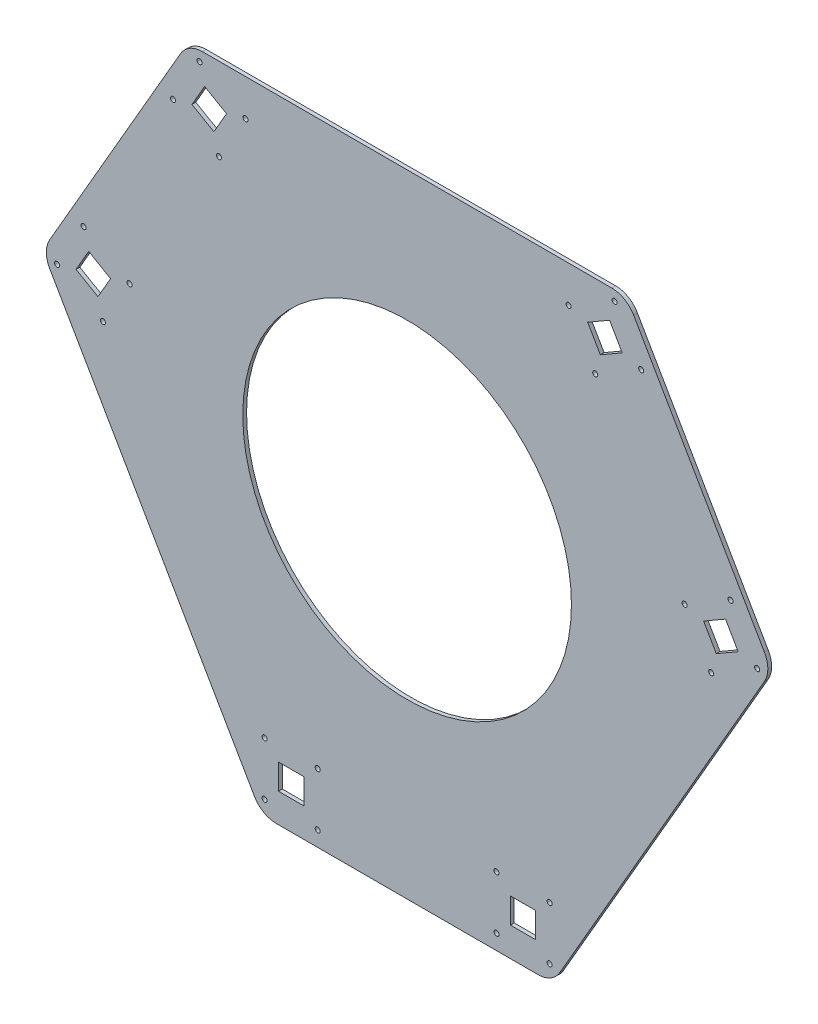
SolidWorks part; units mm, degrees
ref_plane "前视基准面" through (0, 0, 0) normal (0, 0, 1) x (1, 0, 0)
ref_plane "上视基准面" through (0, 0, 0) normal (0, 1, 0) x (1, 0, 0)
ref_plane "右视基准面" through (0, 0, 0) normal (1, 0, 0) x (0, 0, -1)
other "Configuration Table"
sketch "草图1" plane through (0, 0, 0) normal (0, 0, 1) x (1, 0, 0)
  line L0 (173.4394, 232.9258) -> (-173.4394, 232.9258)
  line L1 (-173.4394, 232.9258) -> (-288.4394, 33.74)
  line L2 (-288.4394, 33.74) -> (-115, -266.6658)
  line L3 (-115, -266.6658) -> (115, -266.6658)
  line L4 (115, -266.6658) -> (288.4394, 33.74)
  line L5 (288.4394, 33.74) -> (173.4394, 232.9258)
  line L6 (-230.9394, 133.3329) -> (201.7197, -116.4629) construction
  line L7 (0, 232.9258) -> (0, -266.6658) construction
  circle A0 centre (0, 0) radius 130
  circle A1 centre (164.1865, 224.9521) radius 2
  circle A2 centre (185.1865, 188.579) radius 2
  circle A3 centre (148.8135, 167.579) radius 2
  circle A4 centre (127.8135, 203.9521) radius 2
  circle A5 centre (185.1865, 188.579) radius 2
  circle A6 centre (148.8135, 167.579) radius 2
  circle A7 centre (164.1865, 224.9521) radius 2
  circle A8 centre (127.8135, 203.9521) radius 2
  circle A9 centre (255.9075, 66.0867) radius 2
  circle A10 centre (276.9075, 29.7137) radius 2
  circle A11 centre (240.5344, 8.7137) radius 2
  circle A12 centre (219.5344, 45.0867) radius 2
  circle A13 centre (-164.1865, 224.9521) radius 2
  circle A14 centre (-127.8135, 203.9521) radius 2
  circle A15 centre (-185.1865, 188.579) radius 2
  circle A16 centre (-148.8135, 167.579) radius 2
  circle A17 centre (185.1865, 188.579) radius 2
  circle A18 centre (185.1865, 188.579) radius 2
  circle A19 centre (148.8135, 167.579) radius 2
  circle A20 centre (148.8135, 167.579) radius 2
  circle A21 centre (185.1865, 188.579) radius 2
  circle A22 centre (148.8135, 167.579) radius 2
  circle A23 centre (-219.5344, 45.0867) radius 2 construction
  circle A24 centre (-219.5344, 45.0867) radius 2
  circle A25 centre (-255.9075, 66.0867) radius 2 construction
  circle A26 centre (-255.9075, 66.0867) radius 2
  circle A27 centre (-276.9075, 29.7137) radius 2 construction
  circle A28 centre (-276.9075, 29.7137) radius 2
  circle A29 centre (-240.5344, 8.7137) radius 2 construction
  circle A30 centre (-240.5344, 8.7137) radius 2
  circle A31 centre (-112.7209, -212.6657) radius 2 construction
  circle A32 centre (-112.7209, -212.6657) radius 2
  circle A33 centre (-70.7209, -212.6657) radius 2 construction
  circle A34 centre (-70.7209, -212.6657) radius 2
  circle A35 centre (-112.7209, -254.6657) radius 2 construction
  circle A36 centre (-112.7209, -254.6657) radius 2
  circle A37 centre (-70.7209, -254.6657) radius 2 construction
  circle A38 centre (-70.7209, -254.6657) radius 2
  circle A39 centre (112.7209, -254.6657) radius 2 construction
  circle A40 centre (112.7209, -254.6657) radius 2
  circle A41 centre (70.7209, -254.6657) radius 2 construction
  circle A42 centre (70.7209, -254.6657) radius 2
  circle A43 centre (70.7209, -212.6657) radius 2 construction
  circle A44 centre (70.7209, -212.6657) radius 2
  circle A45 centre (112.7209, -212.6657) radius 2 construction
  circle A46 centre (112.7209, -212.6657) radius 2
  point P7 (0, 0)
  point P70 (-122.2962, -44.0868)
  dimension "D7" = 120
  dimension "D3" = 260
  dimension "D1" = 120
  dimension "D2" = 120
  dimension "D4" = 120
  dimension "D5" = 120
  dimension "D6" = 230
extrude "凸台-拉伸1" add sketch "草图1" along normal blind 3 contours L4 L5 L0 L1 L2 L3 A0 | L5 L0 L1 L2 L3 L4 | A0 | A28 | A46 | A40 | A42 | A44 | A34 | A32 | A38 | A36 | A26 | A24 | A30 | A14 | A16 | A15 | A13 | A10 | A11 | A12 | A9 | A3 | A5 | A7 | A4 region at (224.3304, 129.5172, 0)
sketch "草图8" plane through (0, 0, 3) normal (0, 0, 1) x (1, 0, 0)
  line L0 (-160.1603, 209.9258) -> (-170.1603, 192.6053)
  line L1 (-160.1603, 209.9258) -> (-142.8398, 199.9258)
  line L2 (-170.1603, 192.6053) -> (-152.8398, 182.6053)
  line L3 (-142.8398, 199.9258) -> (-152.8398, 182.6053)
  line L4 (-173.4394, 232.9258) -> (-288.4394, 33.74) construction
  line L5 (-251.8813, 51.0605) -> (-261.8813, 33.74)
  line L6 (-251.8813, 51.0605) -> (-234.5608, 41.0605)
  line L7 (-261.8813, 33.74) -> (-244.5608, 23.74)
  line L8 (-234.5608, 41.0605) -> (-244.5608, 23.74)
  line L9 (-101.7209, -243.6658) -> (-81.7209, -243.6658)
  line L10 (-101.7209, -243.6658) -> (-101.7209, -223.6658)
  line L11 (-81.7209, -243.6658) -> (-81.7209, -223.6658)
  line L12 (-101.7209, -223.6658) -> (-81.7209, -223.6658)
  line L13 (81.7209, -243.6658) -> (101.7209, -243.6658)
  line L14 (81.7209, -243.6658) -> (81.7209, -223.6658)
  line L15 (101.7209, -243.6658) -> (101.7209, -223.6658)
  line L16 (81.7209, -223.6658) -> (101.7209, -223.6658)
  line L17 (261.8813, 33.74) -> (251.8813, 51.0605)
  line L18 (261.8813, 33.74) -> (244.5608, 23.74)
  line L19 (251.8813, 51.0605) -> (234.5608, 41.0605)
  line L20 (244.5608, 23.74) -> (234.5608, 41.0605)
  line L21 (160.1603, 209.9258) -> (170.1603, 192.6053)
  line L22 (160.1603, 209.9258) -> (142.8398, 199.9258)
  line L23 (170.1603, 192.6053) -> (152.8398, 182.6053)
  line L24 (142.8398, 199.9258) -> (152.8398, 182.6053)
  line L25 (-173.4394, 232.9258) -> (-288.4394, 33.74) construction
  line L26 (288.4394, 33.74) -> (173.4394, 232.9258) construction
  line L27 (-115, -266.6658) -> (115, -266.6658) construction
  line L28 (-173.4394, 232.9258) -> (-58.4394, 33.74) construction
  line L29 (-58.4394, 33.74) -> (-288.4394, 33.74) construction
  line L30 (173.4394, 232.9258) -> (58.4394, 33.74) construction
  line L31 (58.4394, 33.74) -> (288.4394, 33.74) construction
  line L32 (-115, -266.6658) -> (0, -67.48) construction
  line L33 (0, -67.48) -> (115, -266.6658) construction
  dimension "D1" = 20
  dimension "D2" = 20
  dimension "D3" = 20
  dimension "D4" = 20
  dimension "D5" = 20
  dimension "D6" = 20
  dimension "D7" = 20
  dimension "D8" = 20
  dimension "D9" = 20
  dimension "D10" = 20
  dimension "D11" = 23
  dimension "D12" = 23
  dimension "D13" = 23
  dimension "D14" = 23
  dimension "D15" = 23
  dimension "D16" = 60
  dimension "D17" = 60
  dimension "D18" = 60
  dimension "D19" = 60
  dimension "D20" = 60
  dimension "D21" = 20
  dimension "D22" = 20
extrude "切除-拉伸4" cut sketch "草图8" against normal through all contours L0 L1 L3 L2 | L5 L6 L8 L7 | L21 L22 L24 L23 | L17 L18 L20 L19 | L9 L10 L12 L11 | L13 L14 L16 L15
fillet "圆角2" radius 20 6 edges at (115, -266.6658, 1.5) (-115, -266.6658, 1.5) (173.4394, 232.9258, 1.5) (288.4394, 33.74, 1.5) (-288.4394, 33.74, 1.5) (-173.4394, 232.9258, 1.5)
